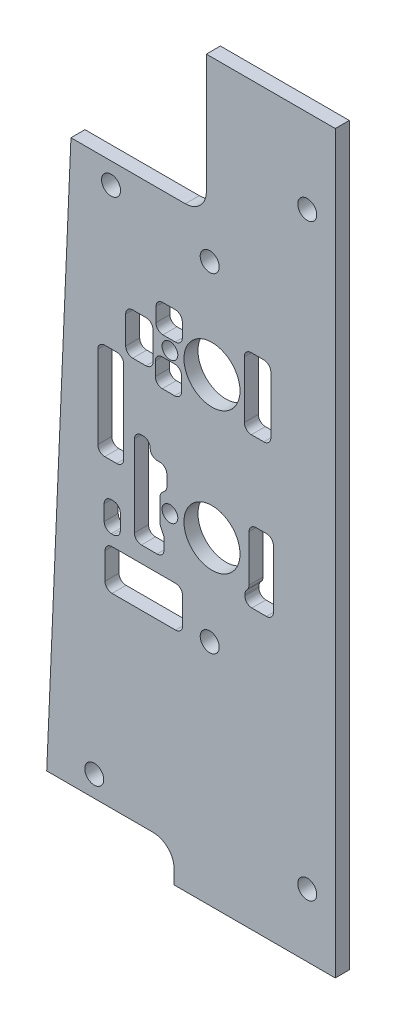
SolidWorks part; units mm, degrees
material "Acrylic (Medium-high impact)"
ref_plane "Front Plane" through (0, 0, 0) normal (0, 0, 1) x (1, 0, 0)
ref_plane "Top Plane" through (0, 0, 0) normal (0, 1, 0) x (1, 0, 0)
ref_plane "Right Plane" through (0, 0, 0) normal (1, 0, 0) x (0, 0, -1)
sketch "Sketch1" plane through (0, 0, 0) normal (0, 0, 1) x (1, 0, 0)
  line L8 (-36.5125, 0) -> (0, 0)
  line L9 (0, 0) -> (0, 166.6875)
  line L10 (0, 166.6875) -> (-29.21, 166.6875)
  line L11 (-29.21, 166.6875) -> (-29.21, 139.7)
  line L12 (-33.9725, 134.9375) -> (-59.8907, 134.9375)
  line L13 (-59.8907, 134.9375) -> (-65.3795, 7.9375)
  line L14 (-65.3795, 7.9375) -> (-41.275, 7.9375)
  line L15 (-36.5125, 3.175) -> (-36.5125, 0)
  line L16 (-36.5125, 0) -> (0, 0)
  line L17 (0, 0) -> (0, 166.6875)
  line L18 (0, 166.6875) -> (-29.21, 166.6875)
  line L19 (-29.21, 166.6875) -> (-29.21, 139.7)
  line L20 (-33.9725, 134.9375) -> (-59.8907, 134.9375)
  line L21 (-59.8907, 134.9375) -> (-65.3795, 7.9375)
  line L22 (-65.3795, 7.9375) -> (-41.275, 7.9375)
  line L23 (-36.5125, 3.175) -> (-36.5125, 0)
  arc A2 (-33.9725, 134.9375) -> (-29.21, 139.7) centre (-33.9725, 139.7) ccw
  arc A3 (-36.5125, 3.175) -> (-41.275, 7.9375) centre (-41.275, 3.175) ccw
  arc A4 (-33.9725, 134.9375) -> (-29.21, 139.7) centre (-33.9725, 139.7) ccw
  arc A5 (-36.5125, 3.175) -> (-41.275, 7.9375) centre (-41.275, 3.175) ccw
  dimension "D1" = 0
extrude "Boss-Extrude1" add sketch "Sketch1" against normal blind 3.175
hole_wizard "9/64 (0.14063) Diameter Hole1" positions "Sketch6" profile "Sketch5" hole size "9/64" standard "ANSI Inch" end condition through all
sketch "Sketch6" plane through (0, 0, 0) normal (0, 0, 1) x (1, 0, 0)
  point P0 (-18.415, 26.3525)
  point P3 (-37.465, 72.39)
  point P6 (-37.465, 104.394)
sketch "Sketch5" plane through (-18.415, 26.3525, 0) normal (1, 0, 0) x (0, -1, 0)
  line L0 (0, 0) -> (0, 3.175)
  line L1 (0, 3.175) -> (1.786, 3.175)
  line L2 (1.786, 3.175) -> (1.786, 0)
  line L5 (1.786, 0) -> (0, 0)
  line L11 (0, -6.35) -> (0, 107.95) construction
  dimension "Thru Hole Dia." = 3.572
  dimension "Thru Hole Depth" = 3.175
hole_wizard "1/2 (0.5) Diameter Hole1" positions "Sketch8" profile "Sketch7" hole size "1/2" standard "ANSI Inch" end condition through all
sketch "Sketch8" plane through (0, 0, 0) normal (0, 0, 1) x (1, 0, 0)
  point P0 (-27.94, 26.3525)
  point P3 (-27.94, 72.39)
  point P6 (-27.94, 104.394)
sketch "Sketch7" plane through (-27.94, 26.3525, 0) normal (1, 0, 0) x (0, -1, 0)
  line L0 (0, 0) -> (0, 3.175)
  line L1 (0, 3.175) -> (6.35, 3.175)
  line L2 (6.35, 3.175) -> (6.35, 0)
  line L5 (6.35, 0) -> (0, 0)
  line L11 (0, -6.35) -> (0, 107.95) construction
  dimension "Thru Hole Dia." = 12.7
  dimension "Thru Hole Depth" = 3.175
hole_wizard "#6 Clearance Hole1" positions "Sketch10" profile "Sketch9" hole size "#6" standard "ANSI Inch" end condition through all
sketch "Sketch10" plane through (0, 0, 0) normal (0, 0, 1) x (1, 0, 0)
  point P0 (-28.448, 51.7525)
  point P3 (-28.448, 126.365)
sketch "Sketch9" plane through (-28.448, 51.7525, 0) normal (1, 0, 0) x (0, -1, 0)
  line L0 (0, 0) -> (0, 3.175)
  line L1 (0, 3.175) -> (2.1526, 3.175)
  line L2 (2.1526, 3.175) -> (2.1526, 0)
  line L5 (2.1526, 0) -> (0, 0)
  line L11 (0, -6.35) -> (0, 107.95) construction
  dimension "Thru Hole Dia." = 4.3053
  dimension "Thru Hole Depth" = 3.175
hole_wizard "#6 Clearance Hole2" positions "Sketch12" profile "Sketch11" hole size "#6" standard "ANSI Inch" end condition through all
sketch "Sketch12" plane through (0, 0, 0) normal (0, 0, 1) x (1, 0, 0)
  point P0 (-50.8, 130.175)
  point P3 (-6.35, 147.6375)
  point P6 (-6.35, 14.2875)
  point P9 (-54.61, 12.7)
sketch "Sketch11" plane through (-50.8, 130.175, 0) normal (1, 0, 0) x (0, -1, 0)
  line L0 (0, 0) -> (0, 3.175)
  line L1 (0, 3.175) -> (2.1526, 3.175)
  line L2 (2.1526, 3.175) -> (2.1526, 0)
  line L5 (2.1526, 0) -> (0, 0)
  line L11 (0, -6.35) -> (0, 107.95) construction
  dimension "Thru Hole Dia." = 4.3053
  dimension "Thru Hole Depth" = 3.175
sketch "Sketch13" plane through (0, 0, 0) normal (0, 0, 1) x (1, 0, 0)
  line L1 (-36.7288, 18.4616) -> (-13.154, 18.4616)
  line L2 (-36.7288, 18.4616) -> (-36.7288, 34.3872)
  line L3 (-36.7288, 34.3872) -> (-13.154, 34.3872)
  line L4 (-13.154, 18.4616) -> (-13.154, 34.3872)
extrude "Boss-Extrude2" add sketch "Sketch13" against normal through all
sketch "Sketch14" plane through (0, 0, 0) normal (0, 0, 1) x (1, 0, 0)
  line L0 (-47.9417, 77.7812) -> (-47.9417, 96.4693)
  line L1 (-49.5292, 98.0568) -> (-52.2259, 98.0568)
  line L2 (-53.8134, 96.4693) -> (-53.8134, 77.7812)
  line L3 (-52.2259, 76.1937) -> (-49.5292, 76.1937)
  line L4 (-45.5032, 83.0253) -> (-45.5032, 64.6066)
  line L5 (-43.9157, 63.0191) -> (-40.3704, 63.0191)
  line L6 (-38.7829, 64.6066) -> (-38.7829, 66.7904)
  line L7 (-38.9351, 67.4686) -> (-39.559, 68.7891)
  line L8 (-39.7112, 69.4674) -> (-39.7112, 74.5143)
  line L9 (-39.198, 75.6831) -> (-38.6678, 76.1704)
  line L10 (-38.1546, 77.3392) -> (-38.1546, 79.7639)
  line L11 (-39.7421, 81.3514) -> (-40.3388, 81.3514)
  line L12 (-41.9263, 82.9389) -> (-41.9263, 83.0253)
  line L13 (-43.5138, 84.6128) -> (-43.9157, 84.6128)
  line L14 (-47.4834, 100.2688) -> (-47.4834, 106.5574)
  line L15 (-45.8959, 108.1449) -> (-42.8844, 108.1449)
  line L16 (-41.2969, 106.5574) -> (-41.2969, 100.2688)
  line L17 (-42.8844, 98.6813) -> (-45.8959, 98.6813)
  line L18 (-34.656, 108.2665) -> (-34.656, 111.4221)
  line L19 (-36.2435, 113.0096) -> (-39.0579, 113.0096)
  line L20 (-40.6454, 111.4221) -> (-40.6454, 108.2665)
  line L21 (-39.0579, 106.679) -> (-36.2435, 106.679)
  line L22 (-34.8187, 97.6361) -> (-34.8187, 100.7008)
  line L23 (-36.4062, 102.2883) -> (-39.1933, 102.2883)
  line L24 (-40.7808, 100.7008) -> (-40.7808, 97.6361)
  line L25 (-39.1933, 96.0486) -> (-36.4062, 96.0486)
  line L26 (-14.6034, 98.6959) -> (-14.6034, 111.6098)
  line L27 (-16.1909, 113.1973) -> (-19.0211, 113.1973)
  line L28 (-20.6086, 111.6098) -> (-20.6086, 98.6959)
  line L29 (-19.0211, 97.1084) -> (-16.1909, 97.1084)
  line L30 (-20.4851, 64.7468) -> (-20.4851, 65.0549)
  line L31 (-20.101, 66.0903) -> (-19.919, 66.3018)
  line L33 (-17.9473, 79.3985) -> (-15.5964, 79.3985)
  line L34 (-14.0089, 77.811) -> (-14.0089, 64.7468)
  line L35 (-15.5964, 63.1593) -> (-18.8976, 63.1593)
  line L36 (-19.5348, 67.3372) -> (-19.5348, 77.811)
  line L37 (-50.7681, 68.4883) -> (-50.2977, 68.4883)
  line L38 (-48.7102, 66.9008) -> (-48.7102, 63.4063)
  line L39 (-50.2977, 61.8188) -> (-50.7681, 61.8188)
  line L40 (-52.3556, 63.4063) -> (-52.3556, 66.9008)
  line L41 (-50.582, 59.3529) -> (-36.1817, 59.3529)
  line L42 (-34.5942, 57.7654) -> (-34.5942, 51.7681)
  line L43 (-36.1817, 50.1806) -> (-50.582, 50.1806)
  line L44 (-52.1695, 51.7681) -> (-52.1695, 57.7654)
  arc A0 (-47.9417, 96.4693) -> (-49.5292, 98.0568) centre (-49.5292, 96.4693) ccw
  arc A1 (-52.2259, 98.0568) -> (-53.8134, 96.4693) centre (-52.2259, 96.4693) ccw
  arc A2 (-53.8134, 77.7812) -> (-52.2259, 76.1937) centre (-52.2259, 77.7812) ccw
  arc A3 (-47.9417, 77.7812) -> (-49.5292, 76.1937) centre (-49.5292, 77.7812) cw
  arc A4 (-45.5032, 83.0253) -> (-43.9157, 84.6128) centre (-43.9157, 83.0253) cw
  arc A5 (-40.3388, 81.3514) -> (-41.9263, 82.9389) centre (-40.3388, 82.9389) cw
  arc A6 (-38.1546, 79.7639) -> (-39.7421, 81.3514) centre (-39.7421, 79.7639) ccw
  arc A7 (-38.6678, 76.1704) -> (-38.1546, 77.3392) centre (-39.7421, 77.3392) ccw
  arc A8 (-39.7112, 74.5143) -> (-39.198, 75.6831) centre (-38.1237, 74.5143) cw
  arc A9 (-39.559, 68.7891) -> (-39.7112, 69.4674) centre (-38.1237, 69.4674) cw
  arc A10 (-38.7829, 66.7904) -> (-38.9351, 67.4686) centre (-40.3704, 66.7904) ccw
  arc A11 (-40.3704, 63.0191) -> (-38.7829, 64.6066) centre (-40.3704, 64.6066) ccw
  arc A12 (-45.5032, 64.6066) -> (-43.9157, 63.0191) centre (-43.9157, 64.6066) ccw
  arc A13 (-41.9263, 83.0253) -> (-43.5138, 84.6128) centre (-43.5138, 83.0253) ccw
  arc A14 (-41.2969, 100.2688) -> (-42.8844, 98.6813) centre (-42.8844, 100.2688) cw
  arc A15 (-42.8844, 108.1449) -> (-41.2969, 106.5574) centre (-42.8844, 106.5574) cw
  arc A16 (-47.4834, 106.5574) -> (-45.8959, 108.1449) centre (-45.8959, 106.5574) cw
  arc A17 (-47.4834, 100.2688) -> (-45.8959, 98.6813) centre (-45.8959, 100.2688) ccw
  arc A18 (-34.656, 111.4221) -> (-36.2435, 113.0096) centre (-36.2435, 111.4221) ccw
  arc A19 (-39.0579, 113.0096) -> (-40.6454, 111.4221) centre (-39.0579, 111.4221) ccw
  arc A20 (-40.6454, 108.2665) -> (-39.0579, 106.679) centre (-39.0579, 108.2665) ccw
  arc A21 (-34.656, 108.2665) -> (-36.2435, 106.679) centre (-36.2435, 108.2665) cw
  arc A22 (-34.8187, 100.7008) -> (-36.4062, 102.2883) centre (-36.4062, 100.7008) ccw
  arc A23 (-39.1933, 102.2883) -> (-40.7808, 100.7008) centre (-39.1933, 100.7008) ccw
  arc A24 (-40.7808, 97.6361) -> (-39.1933, 96.0486) centre (-39.1933, 97.6361) ccw
  arc A25 (-34.8187, 97.6361) -> (-36.4062, 96.0486) centre (-36.4062, 97.6361) cw
  arc A26 (-14.6034, 111.6098) -> (-16.1909, 113.1973) centre (-16.1909, 111.6098) ccw
  arc A27 (-19.0211, 113.1973) -> (-20.6086, 111.6098) centre (-19.0211, 111.6098) ccw
  arc A28 (-14.6034, 98.6959) -> (-16.1909, 97.1084) centre (-16.1909, 98.6959) cw
  arc A29 (-20.6086, 98.6959) -> (-19.0211, 97.1084) centre (-19.0211, 98.6959) ccw
  arc A30 (-19.5348, 77.811) -> (-17.9473, 79.3985) centre (-17.9473, 77.811) cw
  arc A31 (-15.5964, 79.3985) -> (-14.0089, 77.811) centre (-15.5964, 77.811) cw
  arc A32 (-14.0089, 64.7468) -> (-15.5964, 63.1593) centre (-15.5964, 64.7468) cw
  arc A33 (-18.8976, 63.1593) -> (-20.4851, 64.7468) centre (-18.8976, 64.7468) cw
  arc A34 (-19.919, 66.3018) -> (-19.5348, 67.3372) centre (-21.1223, 67.3372) ccw
  arc A35 (-20.4851, 65.0549) -> (-20.101, 66.0903) centre (-18.8976, 65.0549) cw
  arc A37 (-48.7102, 63.4063) -> (-50.2977, 61.8188) centre (-50.2977, 63.4063) cw
  arc A38 (-50.7681, 61.8188) -> (-52.3556, 63.4063) centre (-50.7681, 63.4063) cw
  arc A39 (-50.7681, 68.4883) -> (-52.3556, 66.9008) centre (-50.7681, 66.9008) ccw
  arc A40 (-50.2977, 68.4883) -> (-48.7102, 66.9008) centre (-50.2977, 66.9008) cw
  arc A41 (-34.5942, 51.7681) -> (-36.1817, 50.1806) centre (-36.1817, 51.7681) cw
  arc A42 (-50.582, 50.1806) -> (-52.1695, 51.7681) centre (-50.582, 51.7681) cw
  arc A43 (-50.582, 59.3529) -> (-52.1695, 57.7654) centre (-50.582, 57.7654) ccw
  arc A44 (-36.1817, 59.3529) -> (-34.5942, 57.7654) centre (-36.1817, 57.7654) cw
  dimension "D1" = 1.5875
  dimension "D2" = 1.5875
  dimension "D3" = 1.5875
  dimension "D4" = 1.5875
  dimension "D5" = 1.5875
  dimension "D6" = 1.5875
  dimension "D7" = 1.5875
  dimension "D8" = 1.5875
  dimension "D9" = 1.5875
  dimension "D10" = 1.5875
extrude "Cut-Extrude1" cut sketch "Sketch14" against normal through all
